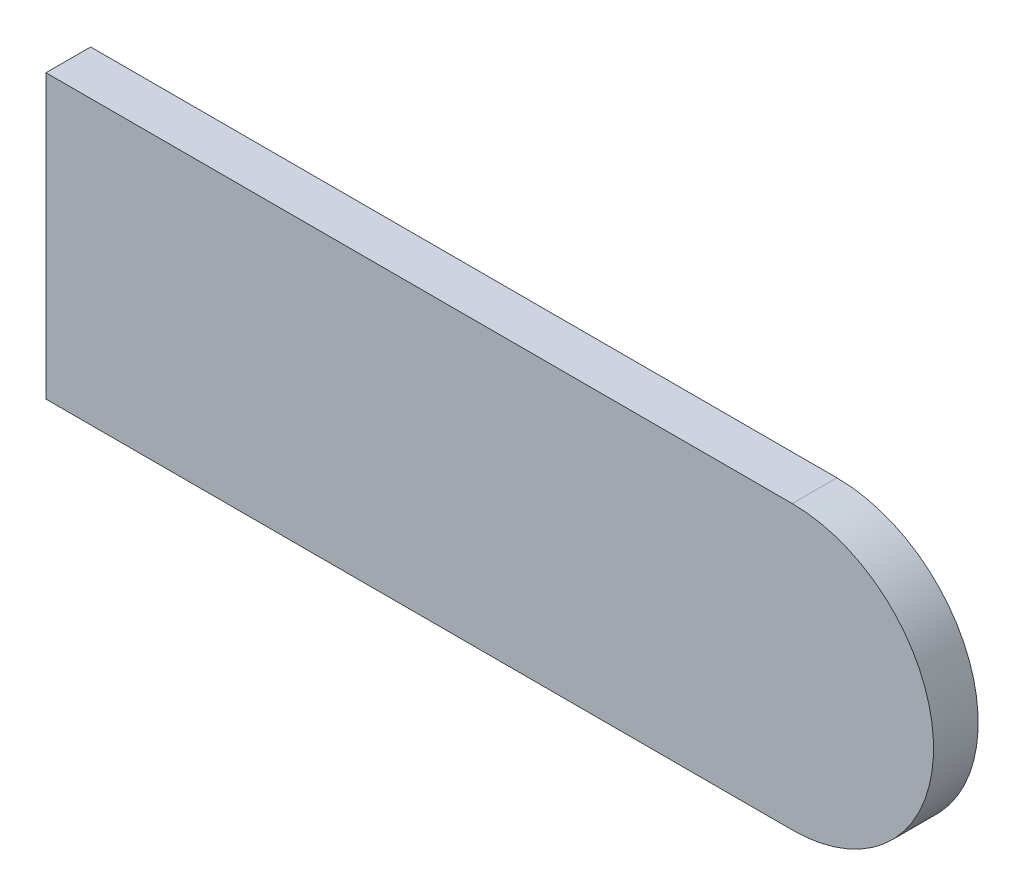
SolidWorks part; units mm, degrees
ref_plane "Front Plane" through (0, 0, 0) normal (0, 0, 1) x (1, 0, 0)
ref_plane "Top Plane" through (0, 0, 0) normal (0, 1, 0) x (1, 0, 0)
ref_plane "Right Plane" through (0, 0, 0) normal (1, 0, 0) x (0, 0, -1)
sketch "Sketch1" plane through (0, 0, 0) normal (0, 0, 1) x (1, 0, 0)
  line L0 (-50.1576, 0) -> (18.2346, 0) construction
  line L1 (-50.1576, -9.5) -> (0, -9.5)
  line L2 (-50.1576, 9.5) -> (-50.1576, -9.5)
  line L3 (-50.1576, 9.5) -> (0, 9.5)
  line L4 (-50.1576, -3.5) -> (-50.1576, 3.5) construction
  line L11 (-13.2776, 9.5) -> (-513.2776, 9.5) construction
  arc A0 (0, -9.5) -> (0, 9.5) centre (0, 0) ccw
extrude "Boss-Extrude1" add sketch "Sketch1" along normal blind 3
